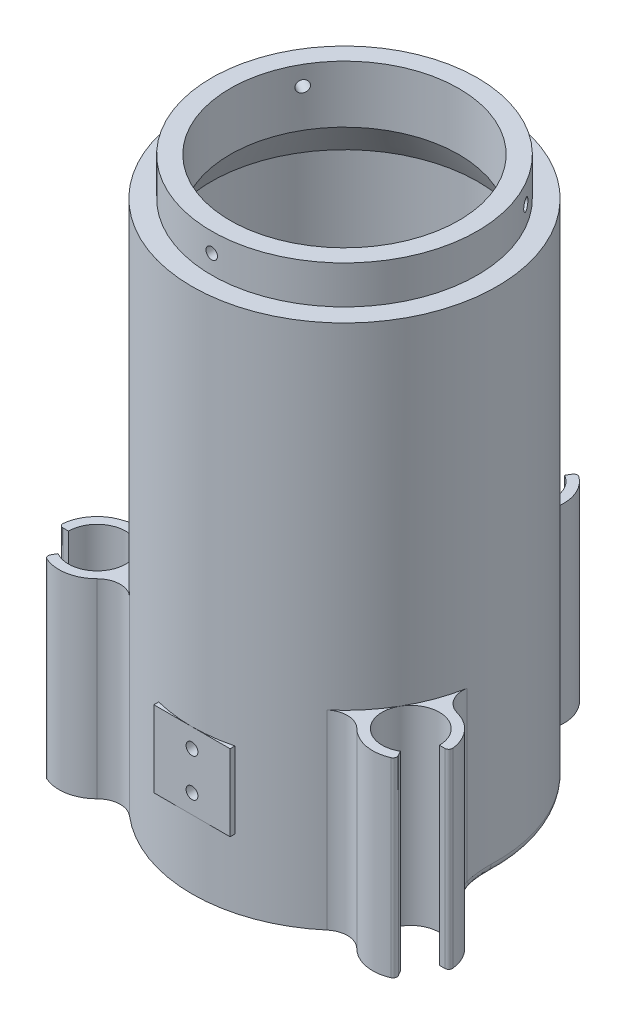
SolidWorks part; units mm, degrees
ref_plane "Front Plane" through (0, 0, 0) normal (0, 0, 1) x (1, 0, 0)
ref_plane "Top Plane" through (0, 0, 0) normal (0, 1, 0) x (1, 0, 0)
ref_plane "Right Plane" through (0, 0, 0) normal (1, 0, 0) x (0, 0, -1)
sketch "Sketch1" plane through (0, 0, 0) normal (0, 1, 0) x (1, 0, 0)
  circle A0 centre (0, 0) radius 40
  circle A1 centre (0, 0) radius 35
  dimension "D1" = 80
  dimension "D2" = 70
extrude "Boss-Extrude1" add sketch "Sketch1" along normal blind 158
sketch "Sketch3" plane through (0, 0, 0) normal (1, 0, 0) x (0, 0, -1)
  line L0 (35, 158) -> (-35, 158) construction
  line L1 (35, 158) -> (-35, 158) construction
  line L2 (-35, 158) -> (-40, 158)
  line L3 (-40, 158) -> (-40, 163)
  line L5 (0, -20.1549) -> (0, 315.4905) construction
  line L10 (0, 188) -> (-20, 188)
  line L11 (-40, 163) -> (-35, 158) construction
  line L12 (0, 188) -> (0, 180.9289)
  line L13 (0, 180.9289) -> (-20, 180.9289)
  line L14 (-20, 188) -> (-20, 180.9289) construction
  line L15 (-32.1, 178.5) -> (-32.1, 167.75) construction
  line L16 (-40, 163) -> (-32.1, 167.75) construction
  spline S0 degree 2 poles (-20, 188) (-35.4489, 179.9814) (-40, 163) knots 0 0 0 1 1 1
  spline S1 degree 2 poles (-20, 180.9289) (-32.9895, 172.5779) (-35, 158) knots 0 0 0 1 1 1
  dimension "D6" = 9.2181
  dimension "D4" = 7.9
  dimension "D3" = 30
  dimension "D1" = 20
  dimension "D2" = 5
  dimension "D5" = 15.5
revolve "Revolve1" add sketch "Sketch3" angle 360 about L5
sketch "Sketch4" plane through (0, 0, 0) normal (0, 1, 0) x (1, 0, 0)
  line L0 (89.2824, 0) -> (-73.0822, 0) construction
  line L1 (0, -55.578) -> (0, 54.7041) construction
  line L2 (0, 47.5) -> (-5, 56.1603) construction
  line L3 (0, 47.5) -> (5, 56.1603) construction
  line L4 (4.4721, 55.246) -> (3.75, 53.9952)
  line L5 (-4.4721, 55.246) -> (-3.75, 53.9952)
  line L6 (45.6083, -31.496) -> (44.8862, -30.2452)
  line L7 (50.0805, -23.75) -> (48.6362, -23.75)
  line L8 (-50.0805, -23.75) -> (-48.6362, -23.75)
  line L9 (-45.6083, -31.496) -> (-44.8862, -30.2452)
  line L10 (-13.432, 37.6773) -> (13.432, 37.6773)
  line L11 (39.3455, -7.2063) -> (25.9136, -30.4711)
  line L12 (-39.3455, -7.2063) -> (-25.9136, -30.4711)
  circle A0 centre (0, 0) radius 40 construction
  arc A1 (13.432, 37.6773) -> (6.0523, 39.5395) centre (0, 0) ccw construction
  arc A2 (-3.75, 53.9952) -> (3.75, 53.9952) centre (0, 47.5) ccw
  arc A4 (9.6542, 44.8931) -> (5.9313, 55.5511) centre (0, 47.5) ccw
  arc A5 (-40, 0) -> (0, -40) centre (0, 0) ccw construction
  arc A6 (0, -40) -> (40, 0) centre (0, 0) ccw construction
  arc A7 (0, 37.5) -> (1.875, 37.6773) centre (0, 47.5) ccw construction
  arc A8 (-1.875, 37.6773) -> (0, 37.5) centre (0, 47.5) ccw construction
  arc A9 (-13.432, 37.6773) -> (-9.6542, 44.8931) centre (-15.4468, 43.3289) ccw
  arc A10 (-9.6542, 44.8931) -> (-13.432, 37.6773) centre (-15.4468, 43.3289) ccw construction
  arc A11 (-13.432, 37.6773) -> (-40, 0) centre (0, 0) ccw construction
  arc A12 (-9.6542, 44.8931) -> (-6.0523, 39.5395) centre (0, 47.5) ccw construction
  arc A13 (9.6542, 44.8931) -> (13.432, 37.6773) centre (15.4468, 43.3289) ccw
  arc A14 (13.432, 37.6773) -> (9.6542, 44.8931) centre (15.4468, 43.3289) ccw construction
  arc A15 (6.0523, 39.5395) -> (9.6542, 44.8931) centre (0, 47.5) ccw construction
  arc A16 (-6.0523, 39.5395) -> (-13.432, 37.6773) centre (0, 0) ccw construction
  arc A17 (6.0523, 39.5395) -> (0, 40) centre (0, 0) ccw construction
  arc A18 (0, 40) -> (-6.0523, 39.5395) centre (0, 0) ccw construction
  arc A19 (40, 0) -> (13.432, 37.6773) centre (0, 0) ccw construction
  arc A20 (-5.9313, 55.5511) -> (-9.6542, 44.8931) centre (0, 47.5) ccw
  arc A21 (5, 56.1603) -> (-5, 56.1603) centre (0, 47.5) ccw construction
  arc A22 (3.75, 53.9952) -> (-3.75, 53.9952) centre (0, 47.5) ccw construction
  arc A23 (5.9313, 55.5511) -> (4.4721, 55.246) centre (5.3382, 54.746) ccw
  arc A24 (-5.9313, 55.5511) -> (-4.4721, 55.246) centre (-5.3382, 54.746) cw
  arc A25 (37.2683, -14.5283) -> (39.3455, -7.2063) centre (0, 0) ccw construction
  arc A27 (39.3455, -7.2063) -> (43.7057, -14.0857) centre (45.2473, -8.2872) ccw
  arc A28 (51.0743, -22.6389) -> (43.7057, -14.0857) centre (41.1362, -23.75) ccw
  arc A30 (25.9136, -30.4711) -> (31.2161, -25.0112) centre (0, 0) ccw construction
  arc A31 (34.0514, -30.8073) -> (25.9136, -30.4711) centre (29.8006, -35.0418) ccw
  arc A32 (34.0514, -30.8073) -> (45.143, -32.9122) centre (41.1362, -23.75) ccw
  arc A33 (48.6362, -23.75) -> (44.8862, -30.2452) centre (41.1362, -23.75) ccw
  arc A34 (45.143, -32.9122) -> (45.6083, -31.496) centre (44.7423, -31.996) ccw
  arc A35 (51.0743, -22.6389) -> (50.0805, -23.75) centre (50.0805, -22.75) cw
  arc A36 (-31.2161, -25.0112) -> (-25.9136, -30.4711) centre (0, 0) ccw construction
  arc A38 (-25.9136, -30.4711) -> (-34.0514, -30.8073) centre (-29.8006, -35.0418) ccw
  arc A39 (-45.143, -32.9122) -> (-34.0514, -30.8073) centre (-41.1362, -23.75) ccw
  arc A41 (-39.3455, -7.2063) -> (-37.2683, -14.5283) centre (0, 0) ccw construction
  arc A42 (-43.7057, -14.0857) -> (-39.3455, -7.2063) centre (-45.2473, -8.2872) ccw
  arc A43 (-43.7057, -14.0857) -> (-51.0743, -22.6389) centre (-41.1362, -23.75) ccw
  arc A44 (-44.8862, -30.2452) -> (-48.6362, -23.75) centre (-41.1362, -23.75) ccw
  arc A45 (-51.0743, -22.6389) -> (-50.0805, -23.75) centre (-50.0805, -22.75) ccw
  arc A46 (-45.143, -32.9122) -> (-45.6083, -31.496) centre (-44.7423, -31.996) cw
  arc A47 (1.875, 37.6773) -> (6.0523, 39.5395) centre (0, 47.5) ccw construction
  arc A48 (-6.0523, 39.5395) -> (-1.875, 37.6773) centre (0, 47.5) ccw construction
  arc A49 (37.2683, -14.5283) -> (33.567, -17.2149) centre (41.1362, -23.75) ccw construction
  arc A50 (31.6921, -20.4624) -> (31.2161, -25.0112) centre (41.1362, -23.75) ccw construction
  arc A51 (32.476, -18.75) -> (31.6921, -20.4624) centre (41.1362, -23.75) ccw [skipped]
  arc A52 (33.567, -17.2149) -> (32.476, -18.75) centre (41.1362, -23.75) ccw [skipped]
  arc A53 (-31.2161, -25.0112) -> (-31.6921, -20.4624) centre (-41.1362, -23.75) ccw construction
  arc A54 (-33.567, -17.2149) -> (-37.2683, -14.5283) centre (-41.1362, -23.75) ccw construction
  arc A55 (-31.6921, -20.4624) -> (-32.476, -18.75) centre (-41.1362, -23.75) ccw [skipped]
  arc A56 (-32.476, -18.75) -> (-33.567, -17.2149) centre (-41.1362, -23.75) ccw [skipped]
  dimension "D1" = 15
  dimension "D2" = 20
  dimension "D3" = 12
  dimension "D4" = 12
  dimension "D7" = 1
  dimension "D5" = 30
  dimension "D6" = 30
  dimension "D8" = 3
extrude "Boss-Extrude2" add sketch "Sketch4" along normal blind 50
ref_plane "Plane1" through (0, 70, 0) normal (0, 1, 0) x (1, 0, 0)
sketch "Sketch6" plane through (0, 70, 0) normal (0, 1, 0) x (1, 0, 0)
  line L0 (0, -46.0373) -> (0, 62.5131) construction
  line L1 (66.4114, 0) -> (-65.7318, 0) construction
  line L2 (-5, 34.641) -> (-5, 11.4564)
  line L3 (5, 34.641) -> (5, 11.4564)
  line L4 (0, 0) -> (62.2869, -35.9614) construction
  line L5 (0, 0) -> (-61.7339, -35.6421) construction
  line L6 (32.9487, -11.8061) -> (12.5, 0)
  line L7 (26.6987, -22.6314) -> (6.25, -10.8253)
  line L8 (-26.6987, -22.6314) -> (-6.25, -10.8253)
  line L9 (-12.5, 0) -> (-32.9487, -11.8061)
  circle A0 centre (0, 0) radius 35 construction
  arc A1 (-32.9487, -11.8061) -> (-26.6987, -22.6314) centre (0, 0) ccw
  arc A2 (12.5, 0) -> (5, 11.4564) centre (0, 0) ccw
  arc A3 (-5, 34.641) -> (-35, 0) centre (0, 0) ccw construction
  arc A4 (-35, 0) -> (-32.9487, -11.8061) centre (0, 0) ccw construction
  arc A5 (26.6987, -22.6314) -> (32.9487, -11.8061) centre (0, 0) ccw
  arc A6 (-26.6987, -22.6314) -> (0, -35) centre (0, 0) ccw construction
  arc A7 (0, -35) -> (26.6987, -22.6314) centre (0, 0) ccw construction
  arc A8 (5, 34.641) -> (-5, 34.641) centre (0, 0) ccw
  arc A9 (32.9487, -11.8061) -> (35, 0) centre (0, 0) ccw construction
  arc A10 (35, 0) -> (5, 34.641) centre (0, 0) ccw construction
  arc A11 (6.25, -10.8253) -> (10.8253, -6.25) centre (0, 0) ccw construction
  arc A12 (10.8253, -6.25) -> (12.5, 0) centre (0, 0) ccw construction
  arc A13 (-5, 11.4564) -> (-12.5, 0) centre (0, 0) ccw
  arc A14 (5, 11.4564) -> (0, 12.5) centre (0, 0) ccw construction
  arc A15 (0, 12.5) -> (-5, 11.4564) centre (0, 0) ccw construction
  arc A16 (-6.25, -10.8253) -> (6.25, -10.8253) centre (0, 0) ccw
  arc A17 (-12.5, 0) -> (-10.8253, -6.25) centre (0, 0) ccw construction
  arc A18 (-10.8253, -6.25) -> (-6.25, -10.8253) centre (0, 0) ccw construction
  circle A19 centre (0, 0) radius 5.5
  dimension "D1" = 25
  dimension "D5" = 11
  dimension "D2" = 10
  dimension "D3" = 30
  dimension "D4" = 30
extrude "Boss-Extrude3" add sketch "Sketch6" along normal blind 8
sketch "Sketch7" plane through (0, 78, 0) normal (0, 1, 0) x (1, 0, 0)
  line L0 (0, 0) -> (0, 18.4139) construction
  circle A0 centre (0, 0) radius 8 construction
  circle A1 centre (0, 8) radius 1.55
  circle A2 centre (8, 0) radius 1.55
  circle A3 centre (0, -8) radius 1.55
  circle A4 centre (-8, 0) radius 1.55
  dimension "D1" = 16
  dimension "D2" = 3.1
  dimension "D3" = 4
extrude "Cut-Extrude1" cut sketch "Sketch7" against normal up to next
sketch "Sketch9" plane through (0, 188, 0) normal (0, 1, 0) x (1, 0, 0)
  circle A0 centre (0, 0) radius 40 construction
  circle A1 centre (0, 0) radius 40
extrude "Cut-Extrude2" cut sketch "Sketch9" against normal blind 50
sketch "Sketch10" plane through (0, 0, 0) normal (0, 0, 1) x (1, 0, 0)
  line L0 (35, 138) -> (-35, 138) construction
  line L1 (35, 138) -> (-35, 138) construction
  line L2 (-35, 124.3397) -> (-30, 133)
  line L3 (-30, 133) -> (-30, 148)
  line L4 (-30, 148) -> (-34.85, 148)
  line L5 (-35, 148) -> (-35, 138) construction
  line L6 (-35, 138) -> (-35, 124.3397)
  line L7 (0, 0) -> (0, 240.5524) construction
  line L9 (-34.85, 138) -> (-34.85, 148)
  line L10 (-34.85, 138) -> (-35, 138)
  line L11 (-34.85, 148) -> (-35, 148) construction
  dimension "D1" = 10
  dimension "D2" = 5
  dimension "D3" = 30
  dimension "D4" = 5
  dimension "D5" = 0.15
revolve "Revolve2" add sketch "Sketch10" angle 360 about L7
ref_plane "Plane2" through (0, 0, 40) normal (0, 0, 1) x (1, 0, 0)
sketch "Sketch11" plane through (0, 0, 40) normal (0, 0, 1) x (1, 0, 0)
  line L1 (40, 138) -> (-40, 138) construction
  line L2 (0, 0) -> (0, 229.7967) construction
  line L3 (40, 138) -> (-40, 138) construction
  circle A0 centre (0, 143) radius 1.5
  circle A1 centre (0, 143) radius 3 construction
  dimension "D1" = 3
  dimension "D3" = 6
  dimension "D2" = 5
extrude "Cut-Extrude3" cut sketch "Sketch11" against normal up to next
pattern_circular "CirPattern1" count 3 over 360 about axis through (0, 148, 0) along (0, -1, 0) of "Cut-Extrude3"
sketch "Sketch12" plane through (0, 0, 40) normal (0, 0, 1) x (1, 0, 0)
  line L0 (0, 0) -> (0, 124.7161) construction
  line L1 (0, 33) -> (0, 23) construction
  line L5 (-10, 18) -> (10, 18) construction
  line L8 (-10, 18) -> (-10, 38) construction
  line L9 (-10, 38) -> (10, 38) construction
  line L10 (10, 18) -> (10, 38) construction
  line L11 (0, 38) -> (0, 18) construction
  line L12 (-10, 28) -> (10, 28) construction
  line L13 (0, 23) -> (0, 33) construction
  circle A4 centre (0, 33) radius 1.55
  circle A5 centre (0, 23) radius 1.55
  point P7 (0, 28)
  point P11 (0, 28)
  point P13 (0, 28)
  dimension "D1" = 3.1
  dimension "D2" = 10
  dimension "D3" = 18
  dimension "D5" = 20
extrude "Cut-Extrude4" cut sketch "Sketch12" against normal up to next
sketch "Sketch13" plane through (0, 0, 40) normal (0, 0, 1) x (1, 0, 0)
  line L0 (0, 23) -> (0, 33) construction
  line L2 (-10, 18) -> (10, 18)
  line L3 (-10, 18) -> (-10, 38)
  line L4 (-10, 38) -> (10, 38)
  line L5 (10, 18) -> (10, 38)
  line L6 (0, 38) -> (0, 18) construction
  line L7 (-10, 28) -> (10, 28) construction
  circle A0 centre (0, 33) radius 1.55
  circle A1 centre (0, 23) radius 1.55
  circle A2 centre (0, 23) radius 1.55 construction
  circle A3 centre (0, 33) radius 1.55 construction
  point P0 (0, 33)
  point P1 (0, 23)
  point P7 (0, 28)
  point P8 (0, 28)
  dimension "D1" = 20
extrude "Boss-Extrude4" add sketch "Sketch13" against normal blind 2
ref_plane "Plane4" through (34.641, 0, -20) normal (0.866, 0, -0.5) x (0, -1, 0)
sketch "Sketch14" plane through (34.641, 0, -20) normal (0.866, 0, -0.5) x (0, -1, 0)
  line L0 (0, 0) -> (-50000, 0) construction
  line L1 (0, -20) -> (0, 20) construction
  line L2 (0, -25.9136) -> (0, 25.9136) construction
  line L3 (-5, -20) -> (-5, 20)
  line L4 (5, -20) -> (5, 20)
  arc A3 (-5, -20) -> (5, -20) centre (0, -20) ccw
  arc A4 (5, 20) -> (-5, 20) centre (0, 20) ccw
  point P9 (0, 0)
  dimension "D1" = 10
  dimension "D2" = 20
extrude "Cut-Extrude5" cut sketch "Sketch14" against normal up to next
fillet "Fillet1" radius 2.5 6 edges at (9.6072, 2.4775, -33.6556) (34.1539, 3.3614, 7.6494) (15.4327, 2.6458, -36.903) (39.7531, 3.3413, 4.4376) (30.3109, 5, -17.5) (34.641, 5, -20)
